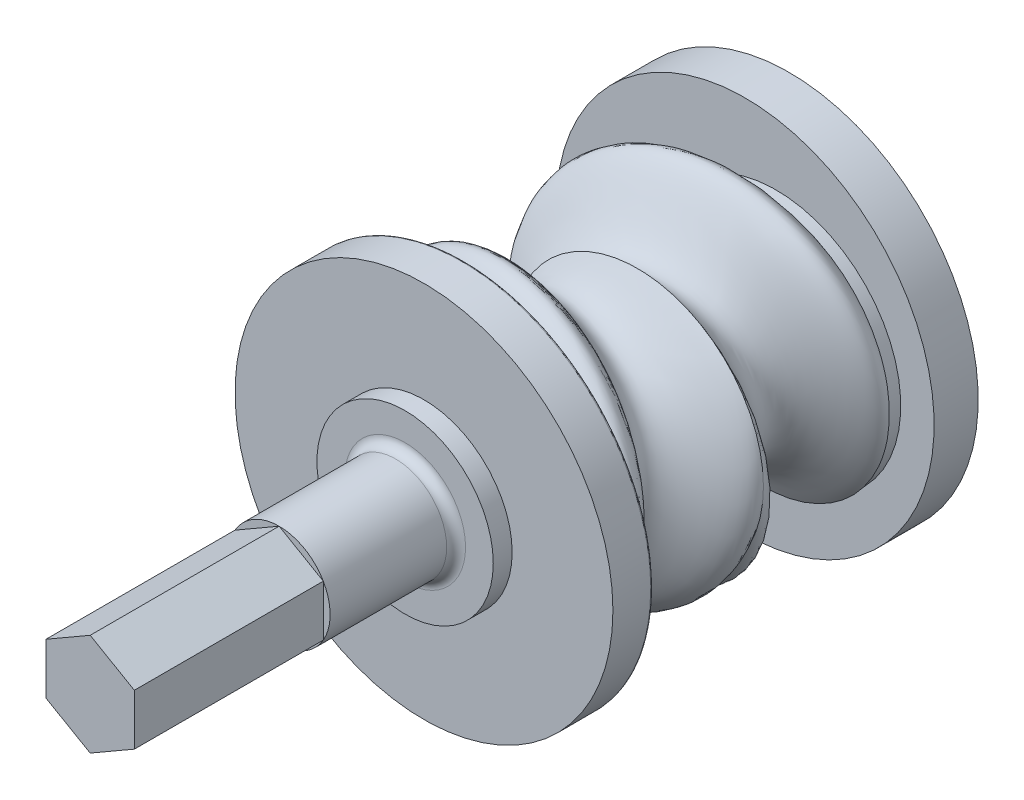
SolidWorks part; units mm, degrees
ref_plane "Ebene vorne" through (0, 0, 0) normal (0, 0, 1) x (1, 0, 0)
ref_plane "Ebene oben" through (0, 0, 0) normal (0, 1, 0) x (1, 0, 0)
ref_plane "Ebene rechts" through (0, 0, 0) normal (1, 0, 0) x (0, 0, -1)
sketch "Skizze2" plane through (0, 0, 0) normal (0, 0, 1) x (1, 0, 0)
  circle A0 centre (0, 0) radius 10
  dimension "D1" = 20
ref_plane "Ebene1" through (0, 0, 0) normal (0, 0, 1) x (1, 0, 0)
sketch "Skizze3" plane through (0, 0, 0) normal (0, 0, 1) x (1, 0, 0)
  circle A0 centre (-2.45, 0) radius 2.2
  point P0 (-2.45, 0)
  dimension "D2" = 4.4
  dimension "D1" = 2.45
curve "Spirale/Helix1" pitch 10 height 10 radius 2.2 left hand yes centre (-2.45, 0, 0) axis (0, 0, 1) start towards (1, 0, 0)
sweep "Austragung1" add profiles "Skizze2" path "Spirale/Helix1"
sketch "Skizze5" plane through (0, 0, 10) normal (0, 0, 1) x (1, 0, 0)
  circle A1 centre (0, 0) radius 9.8996
ref_plane "Ebene3" through (-0.25, 0, 0) normal (0, -0.8102, 0.5861) x (1, 0, 0)
extrude "Schnitt-Linear austragen2" cut sketch "Skizze3<2>" along normal blind 10
sketch "Skizze3<2>" plane through (0, 0, 0) normal (0, 0, 1) x (1, 0, 0) same geometry as "Skizze3"
ref_axis "Achse2" through (-2.45, 0, 55.3086) along (0, 0, -1)
extrude "Aufsatz-Linear austragen3" add sketch "Skizze5" along normal blind 1
sketch "Skizze11" plane through (0, 0, 0) normal (0, 0, -1) x (-1, 0, 0)
  circle A0 centre (0, 0) radius 10
  dimension "D1" = 20
sketch "Skizze16" plane through (0, 0, 11) normal (0, 0, 1) x (1, 0, 0)
  circle A0 centre (-2.45, 0) radius 15
  dimension "D1" = 30
extrude "Aufsatz-Linear austragen7" add sketch "Skizze16" along normal blind 3.5
fillet "Verrundung4" radius 2 1 edges at (12.55, 0, 11) second distance 0.5 first distance on face at (9.8996, 0, 11)
sketch "Skizze19" plane through (0, 0, 14.5) normal (0, 0, 1) x (1, 0, 0)
  circle A0 centre (-2.45, 0) radius 7
  dimension "D1" = 14
extrude "Aufsatz-Linear austragen9" add sketch "Skizze19" along normal blind 1.5
sketch "Skizze21" plane through (0, 0, 16) normal (0, 0, 1) x (1, 0, 0)
  circle A0 centre (-2.45, 0) radius 4.05
  dimension "D1" = 8.1
extrude "Aufsatz-Linear austragen11" add sketch "Skizze21" along normal blind 10
sketch "Skizze22" plane through (0, 0, 26) normal (0, 0, 1) x (1, 0, 0)
  line L1 (-2.45, -4.05) -> (1.0574, -2.025)
  line L2 (1.0574, -2.025) -> (1.0574, 2.025)
  line L3 (1.0574, 2.025) -> (-2.45, 4.05)
  line L4 (-2.45, 4.05) -> (-5.9574, 2.025)
  line L5 (-5.9574, 2.025) -> (-5.9574, -2.025)
  line L6 (-5.9574, -2.025) -> (-2.45, -4.05)
  circle A0 centre (-2.45, 0) radius 3.5074 construction
  circle A1 centre (-2.45, 0) radius 4.05 construction
  dimension "D1" = 8.1
  dimension "D2" = 8.1
extrude "Aufsatz-Linear austragen12" add sketch "Skizze22" along normal blind 15
sketch "Skizze29" plane through (0, 0, 41) normal (0, 0, 1) x (1, 0, 0)
  circle A0 centre (-2.45, 0) radius 2
  dimension "D1" = 4
fillet "Verrundung6" radius 0.75 1 edges at (1.6, 0, 16)
sketch "Skizze30" plane through (0, 0, 0) normal (0, 0, -1) x (-1, 0, 0)
  circle A0 centre (2.45, 0) radius 2.2
curve "Spirale/Helix2" pitch 10 height 10 radius 2.2 centre (-2.45, 0, 0) axis (0, 0, -1) start towards (1, 0, 0)
sweep "Austragung2" add profiles "Skizze11" path "Spirale/Helix2"
sketch "Skizze31" plane through (0, 0, -10) normal (0, 0, -1) x (-1, 0, 0)
  circle A0 centre (0, 0) radius 9.8996
extrude "Aufsatz-Linear austragen14" add sketch "Skizze31" along normal blind 1
sketch "Skizze32" plane through (0, 0, -11) normal (0, 0, -1) x (-1, 0, 0)
  circle A0 centre (2.45, 0) radius 15
extrude "Aufsatz-Linear austragen15" add sketch "Skizze32" along normal blind 3.5
sketch "Skizze33" plane through (0, 0, -14.5) normal (0, 0, -1) x (-1, 0, 0)
  circle A0 centre (2.45, 0) radius 2.2
sketch "Skizze38" plane through (0, 0, -14.5) normal (0, 0, -1) x (-1, 0, 0)
  circle A0 centre (2.45, 0) radius 7
extrude "Aufsatz-Linear austragen17" add sketch "Skizze38" along normal blind 1.5
sketch "Skizze39" plane through (0, 0, -16) normal (0, 0, -1) x (-1, 0, 0)
  circle A1 centre (2.45, 0) radius 2.2
extrude "Schnitt-Linear austragen5" cut sketch "Skizze39" against normal blind 15
thread "Gewinde6" pitch 0.8 method cut profile "Gewindeprofil7" start angle 0, offset 0, length 13, pitch 0.8, diameter 4.4
ref_plane "Ebene10" through (-0.25, 0, -16) normal (0, -1, 0) x (1, 0, 0)
sketch "Gewindeprofil7" plane through (-0.25, 0, -16) normal (0, -1, 0) x (1, 0, 0)
  line L0 (0, 0) -> (0, 0.8) construction
  line L1 (0, 0) -> (0.433, 0.25)
  line L2 (0.433, 0.25) -> (0.433, 0.35)
  line L3 (0.433, 0.35) -> (0, 0.6)
  line L4 (0.433, 0.3) -> (0, 0.3) construction
  line L11 (0, 0) -> (0, 0.6)
  point P2 (0, 0)
  dimension "Pitch" = 0.8
  dimension "Profile_Angle" = 60
  dimension "Profile_Land" = 0.1
  dimension "Profile_Height" = 0.433
